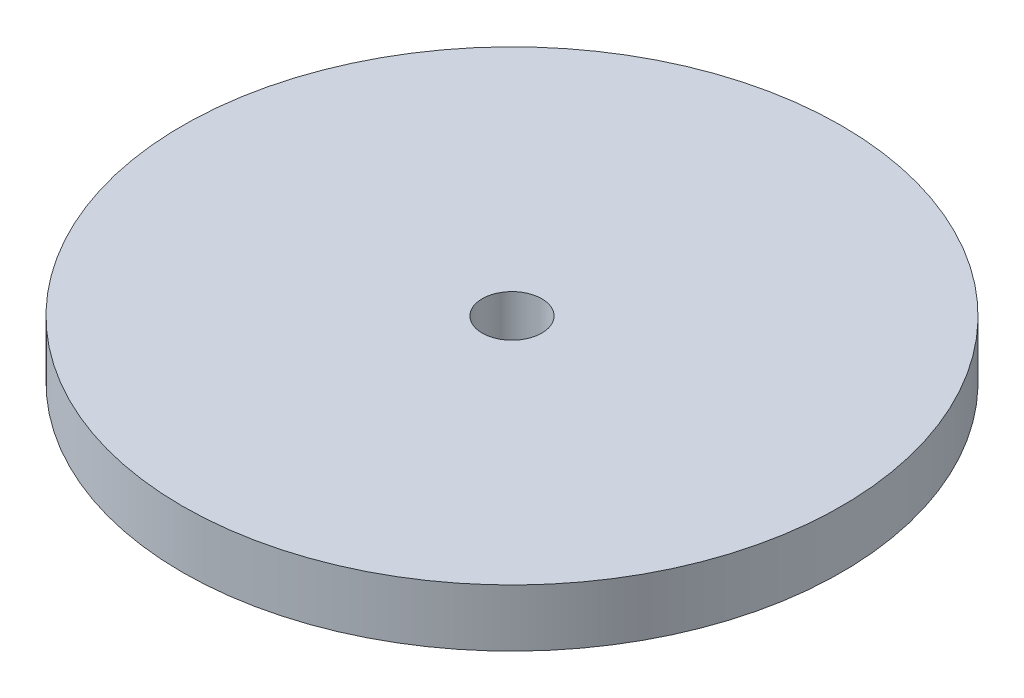
SolidWorks part; units mm, degrees
material "G10 Fiberglass"
ref_plane "Front Plane" through (0, 0, 0) normal (0, 0, 1) x (1, 0, 0)
ref_plane "Top Plane" through (0, 0, 0) normal (0, 1, 0) x (1, 0, 0)
ref_plane "Right Plane" through (0, 0, 0) normal (1, 0, 0) x (0, 0, -1)
sketch "Sketch1" plane through (0, 0, 0) normal (0, 1, 0) x (1, 0, 0)
  circle A0 centre (0, 0) radius 36.5125
  circle A1 centre (0, 0) radius 3.302
  dimension "D1" = 73.025
  dimension "D2" = 6.604
extrude "Boss-Extrude1" add sketch "Sketch1" along normal blind 6.35
ref_axis "Axis1" through (0, -0.3175, 0) along (0, 1, 0)
